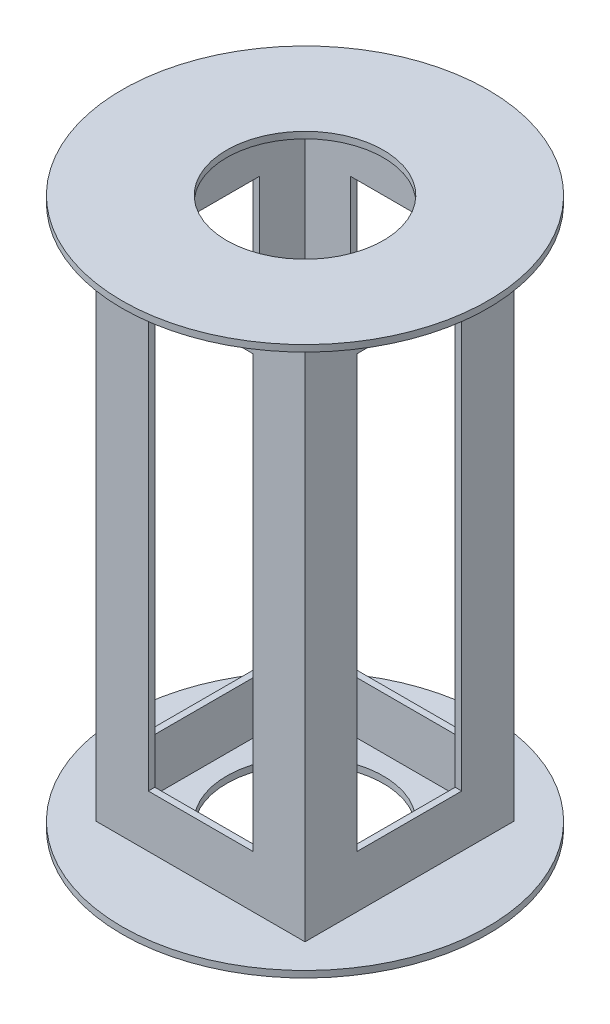
SolidWorks part; units mm, degrees
ref_plane "Front Plane" through (0, 0, 0) normal (0, 0, 1) x (1, 0, 0)
ref_plane "Top Plane" through (0, 0, 0) normal (0, 1, 0) x (1, 0, 0)
ref_plane "Right Plane" through (0, 0, 0) normal (1, 0, 0) x (0, 0, -1)
sketch "Sketch2" plane through (0, 0, 0) normal (0, 1, 0) x (1, 0, 0)
  line L0 (-47.625, 47.625) -> (47.625, 47.625)
  line L1 (-50.8, -50.8) -> (50.8, -50.8)
  line L2 (-50.8, -50.8) -> (-50.8, 50.8)
  line L3 (-50.8, 50.8) -> (50.8, 50.8)
  line L4 (50.8, -50.8) -> (50.8, 50.8)
  line L5 (-50.8, -50.8) -> (50.8, 50.8) construction
  line L6 (-50.8, 50.8) -> (50.8, -50.8) construction
  line L7 (47.625, -47.625) -> (47.625, 47.625)
  line L8 (-47.625, -47.625) -> (47.625, -47.625)
  line L9 (-47.625, -47.625) -> (-47.625, 47.625)
  circle A0 centre (0, 0) radius 88.9
  circle A1 centre (0, 0) radius 38.1
  dimension "D1" = 177.8
  dimension "D2" = 76.2
  dimension "D3" = 101.6
  dimension "D4" = 3.175
extrude "Boss-Extrude1" add sketch "Sketch2" along normal blind 3.175 contours A0 L4 L1 L2 L3 | L1 L4 L3 L2 A1 | L0 L7 L8 L9 | A1 region at (0, 0, -46.278) region at (-49.3632, 0, 0) region at (-86.3855, 0, 0)
extrude "Boss-Extrude2" add sketch "Sketch2<4>" along normal blind 266.7 contours L1 L4 L3 L2 L8 L9 L0 L7 region at (-49.3632, 0, 0)
sketch "Sketch2<4>" plane through (0, 0, 0) normal (0, 1, 0) x (1, 0, 0) same geometry as "Sketch2"
sketch "Sketch3" plane through (0, 266.7, 0) normal (0, 1, 0) x (1, 0, 0)
  circle A0 centre (0, 0) radius 38.1 construction
  circle A1 centre (0, 0) radius 88.9 construction
  circle A2 centre (0, 0) radius 38.1
  circle A3 centre (0, 0) radius 88.9
extrude "Boss-Extrude3" add sketch "Sketch3" against normal blind 3.175
sketch "Sketch4" plane through (0, 0, 0) normal (0, 0, 1) x (1, 0, 0)
  line L4 (50.8, 263.525) -> (-50.8, 263.525)
  line L5 (-50.8, 263.525) -> (-50.8, 3.175)
  line L6 (-50.8, 3.175) -> (50.8, 3.175)
  line L7 (50.8, 3.175) -> (50.8, 263.525)
  line L8 (50.8, 263.525) -> (-50.8, 263.525) construction
  line L9 (-50.8, 263.525) -> (-50.8, 3.175) construction
  line L10 (-50.8, 3.175) -> (50.8, 3.175) construction
  line L11 (50.8, 3.175) -> (50.8, 263.525) construction
  line L16 (25.4, 238.125) -> (-25.4, 238.125)
  line L17 (-25.4, 238.125) -> (-25.4, 28.575)
  line L18 (-25.4, 28.575) -> (25.4, 28.575)
  line L19 (25.4, 28.575) -> (25.4, 238.125)
  line L20 (25.4, 238.125) -> (-25.4, 238.125)
  line L21 (-25.4, 238.125) -> (-25.4, 28.575)
  line L22 (-25.4, 28.575) -> (25.4, 28.575)
  line L23 (25.4, 28.575) -> (25.4, 238.125)
  dimension "D1" = 0
  dimension "D2" = 25.4
extrude "Cut-Extrude1" cut sketch "Sketch4" against normal through all both and the other way through all
sketch "Sketch5" plane through (0, 0, 0) normal (1, 0, 0) x (0, 0, -1)
  line L4 (50.8, 263.525) -> (-50.8, 263.525)
  line L5 (-50.8, 263.525) -> (-50.8, 3.175)
  line L6 (-50.8, 3.175) -> (50.8, 3.175)
  line L7 (50.8, 3.175) -> (50.8, 263.525)
  line L8 (50.8, 263.525) -> (-50.8, 263.525) construction
  line L9 (-50.8, 263.525) -> (-50.8, 3.175) construction
  line L10 (-50.8, 3.175) -> (50.8, 3.175) construction
  line L11 (50.8, 3.175) -> (50.8, 263.525) construction
  line L16 (25.4, 238.125) -> (-25.4, 238.125)
  line L17 (-25.4, 238.125) -> (-25.4, 28.575)
  line L18 (-25.4, 28.575) -> (25.4, 28.575)
  line L19 (25.4, 28.575) -> (25.4, 238.125)
  line L20 (25.4, 238.125) -> (-25.4, 238.125)
  line L21 (-25.4, 238.125) -> (-25.4, 28.575)
  line L22 (-25.4, 28.575) -> (25.4, 28.575)
  line L23 (25.4, 28.575) -> (25.4, 238.125)
  dimension "D1" = 0
  dimension "D2" = 25.4
extrude "Cut-Extrude2" cut sketch "Sketch5" against normal through all both and the other way through all
